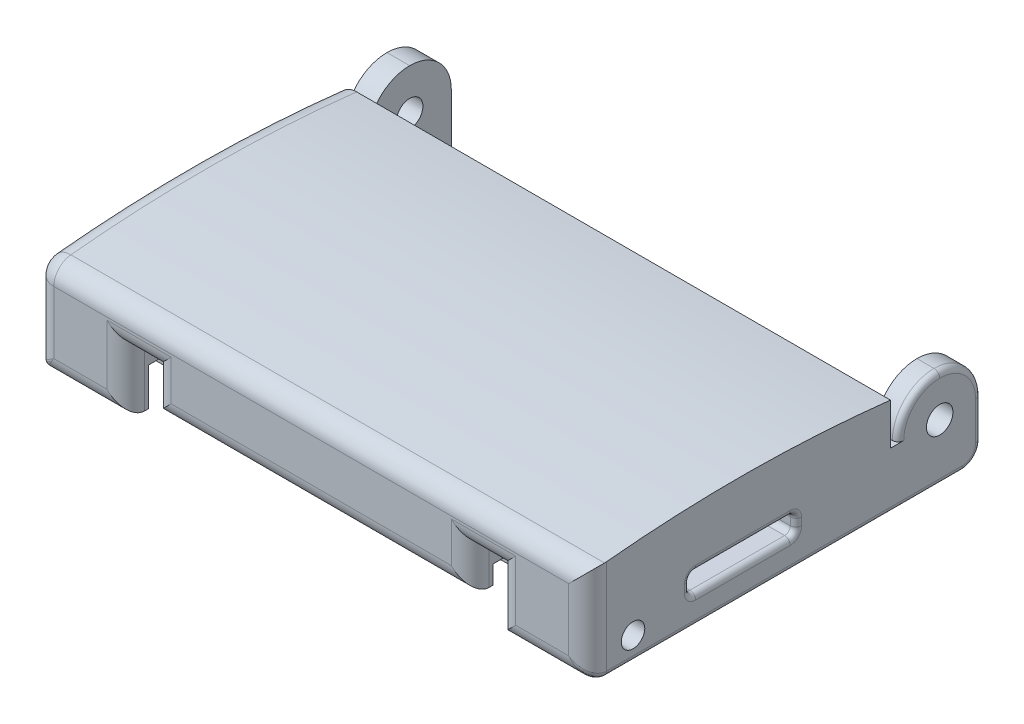
SolidWorks part; units mm, degrees
ref_plane "Front Plane" through (0, 0, 0) normal (0, 0, 1) x (1, 0, 0)
ref_plane "Top Plane" through (0, 0, 0) normal (0, 1, 0) x (1, 0, 0)
ref_plane "Right Plane" through (0, 0, 0) normal (1, 0, 0) x (0, 0, -1)
sketch "Sketch1" plane through (0, 0, 0) normal (0, 1, 0) x (1, 0, 0)
  line L1 (0, 0) -> (18.542, 0)
  line L2 (0, 0) -> (0, 10.16)
  line L3 (0, 10.16) -> (18.542, 10.16)
  line L4 (18.542, 0) -> (18.542, 10.16)
  dimension "D1" = 18.542
  dimension "D2" = 10.16
extrude "Extrude1" add sketch "Sketch1" along normal blind 3.302
sketch "Sketch2" plane through (18.542, 0, 0) normal (1, 0, 0) x (0, 0, -1)
  line L0 (10.16, 3.302) -> (10.16, 0) construction
  line L1 (0, 3.302) -> (10.16, 3.302) construction
  line L2 (0, 3.302) -> (0, 2.5771)
  line L3 (0, 3.302) -> (0, 0) construction
  line L4 (0, 2.5771) -> (10.16, 2.5771)
  line L5 (10.16, 2.5771) -> (10.16, 3.302)
  arc A0 (0, 3.302) -> (10.16, 3.302) centre (5.08, -41.3095) cw
  dimension "D1" = 44.6115
extrude "Extrude2" add sketch "Sketch2" against normal up to surface (18.542 mm away) up to face at (0, 1.651, -5.08)
sketch "Sketch3" plane through (0, 0, 0) normal (0, 0, 1) x (1, 0, 0)
  line L2 (15.494, 2.0076) -> (15.494, 0)
  line L3 (0, 0) -> (18.542, 0) construction
  line L4 (3.937, 0.6534) -> (14.605, 0.6534)
  line L5 (15.494, 0) -> (3.048, 0)
  line L8 (14.605, 0.6534) -> (14.605, 2.0076)
  line L9 (14.605, 2.0076) -> (15.494, 2.0076)
  line L12 (3.937, 0.6534) -> (3.937, 2.0076)
  line L13 (3.937, 2.0076) -> (3.048, 2.0076)
  line L14 (3.048, 0) -> (3.048, 2.0076)
  point P0 (9.271, 0)
  point P12 (9.271, 0.6534)
  dimension "D1" = 10.668
  dimension "D2" = 0.889
  dimension "D3" = 0.889
extrude "Extrude3" cut sketch "Sketch3" against normal blind 2.286
sketch "Sketch4" plane through (0, 0, 0) normal (0, -1, 0) x (1, 0, 0)
  line L0 (0, 0) -> (3.048, 0) construction
  line L1 (0.762, -2.286) -> (3.048, -2.286)
  line L2 (0.762, -2.286) -> (0.762, -0.762)
  line L3 (0.762, -0.762) -> (17.78, -0.762)
  line L4 (17.78, -2.286) -> (17.78, -0.762)
  line L5 (0, -10.16) -> (0, 0) construction
  line L6 (18.542, 0) -> (18.542, -10.16) construction
  line L7 (14.605, -2.286) -> (3.937, -2.286) construction
  line L8 (14.605, -2.286) -> (14.605, 0) construction
  line L9 (15.494, -2.286) -> (17.78, -2.286)
  line L10 (3.048, -2.286) -> (3.048, -3.129)
  line L11 (3.048, -3.129) -> (3.937, -3.129)
  line L12 (3.937, -2.286) -> (3.937, -3.129)
  line L14 (15.494, -2.286) -> (15.494, -3.129)
  line L15 (15.494, -3.129) -> (14.605, -3.129)
  line L16 (14.605, -2.286) -> (14.605, -3.129)
  line L17 (3.937, -2.286) -> (3.937, 0) construction
  line L18 (3.937, -2.286) -> (14.605, -2.286)
  dimension "D1" = 0.762
  dimension "D2" = 0.762
  dimension "D3" = 0.762
extrude "Extrude4" cut sketch "Sketch4" against normal blind 1.27
sketch "Sketch5" plane through (0.762, 0, 0) normal (1, 0, 0) x (0, 0, -1)
  line L0 (2.286, 0.7907) -> (0.762, 0.7907) construction
  line L1 (2.286, 1.27) -> (2.286, 0) construction
  line L2 (0.762, 1.27) -> (0.762, 0) construction
  circle A0 centre (1.524, 0.7907) radius 0.3937
  dimension "D1" = 0.7874
extrude "Extrude5" cut sketch "Sketch5" against normal mid plane 40.386
chamfer "Chamfer1" distance 0.762 angle 45 2 edges at (3.4925, 1.27, -2.286) (15.0495, 1.27, -2.286)
sketch "Sketch6" plane through (0, 0, 0) normal (0, -1, 0) x (1, 0, 0)
  line L0 (0, -5.08) -> (18.542, -5.08) construction
  line L1 (7.874, -3.1797) -> (10.668, -3.1797)
  line L2 (7.874, -3.1797) -> (7.874, -7.2437)
  line L3 (7.874, -7.2437) -> (10.668, -7.2437)
  line L4 (10.668, -3.1797) -> (10.668, -7.2437)
  line L5 (0, -10.16) -> (0, 0) construction
  line L6 (18.542, 0) -> (18.542, -10.16) construction
  point P10 (9.271, -5.08)
  point P11 (9.271, -3.1797)
  dimension "D1" = 2.794
  dimension "D2" = 4.064
extrude "Extrude6" cut sketch "Sketch6" against normal blind 2.54
sketch "Sketch7" plane through (10.668, 0, 0) normal (-1, 0, 0) x (0, 0, 1)
  line L0 (-6.9897, 1.5875) -> (-3.4337, 0.9525) construction
  line L1 (-3.4337, 0.9525) -> (-6.9897, 0.9525)
  line L2 (-3.4337, 0.9525) -> (-3.4337, 1.5875)
  line L3 (-3.4337, 1.5875) -> (-6.9897, 1.5875)
  line L4 (-6.9897, 0.9525) -> (-6.9897, 1.5875)
  line L5 (-7.2437, 0) -> (-3.1797, 2.54) construction
  point P8 (-5.2117, 1.27)
  point P9 (-5.2117, 1.27)
  dimension "D1" = 0.635
  dimension "D2" = 3.556
extrude "Extrude7" cut sketch "Sketch7" against normal mid plane 22.86
sketch "Sketch8" plane through (0, 0, 0) normal (0, -1, 0) x (1, 0, 0)
  line L0 (10.668, -3.1797) -> (7.874, -3.1797) construction
  line L1 (7.874, -7.2437) -> (10.668, -7.2437) construction
  line L2 (7.874, -3.1797) -> (7.874, -4.099)
  line L3 (7.874, -4.099) -> (7.874, -7.2437)
  line L4 (10.668, -7.2437) -> (10.668, -3.1797)
  arc A0 (7.874, -3.1797) -> (10.668, -3.1797) centre (9.271, -6.8945) cw
  arc A1 (7.874, -7.2437) -> (10.668, -7.2437) centre (9.271, -3.529) ccw
  point P8 (9.271, -7.4977)
  point P11 (9.271, -2.9257)
  point P12 (9.271, -3.1797)
  point P15 (9.271, -7.2437)
  dimension "D1" = 0.254
  dimension "D2" = 0.254
extrude "Extrude8" cut sketch "Sketch8" against normal up to surface (2.54 mm away) up to face at (9.271, 2.54, -5.2117)
fillet "Fillet1" radius 0.1905 24 edges at (18.542, 1.27, -6.9897) (10.668, 1.27, -6.9897) (18.542, 1.5875, -5.2117) (14.605, 1.5875, -6.9897) (10.668, 1.5875, -5.2117) (18.542, 0.9525, -5.2117) (10.668, 0.9525, -5.2117) (14.605, 0.9525, -6.9897) (18.542, 1.27, -3.4337) (14.605, 1.5875, -3.4337) (10.668, 1.27, -3.4337) (14.605, 0.9525, -3.4337) (0, 1.27, -6.9897) (7.874, 1.27, -6.9897) (0, 0.9525, -5.2117) (3.937, 0.9525, -6.9897) (7.874, 0.9525, -5.2117) (0, 1.27, -3.4337) (3.937, 0.9525, -3.4337) (7.874, 1.27, -3.4337) (0, 1.5875, -5.2117) (3.937, 1.5875, -3.4337) (7.874, 1.5875, -5.2117) (3.937, 1.5875, -6.9897)
sketch "Sketch9" plane through (0, 0, -10.16) normal (0, 0, -1) x (-1, 0, 0)
  line L1 (-18.542, 0) -> (-17.8308, 0)
  line L2 (-18.542, 0) -> (-18.542, 1.905)
  line L3 (-18.542, 1.905) -> (-17.8308, 1.905)
  line L4 (-17.8308, 0) -> (-17.8308, 1.905)
  dimension "D1" = 0.7112
  dimension "D2" = 1.905
extrude "Extrude9" add sketch "Sketch9" along normal blind 0.254
sketch "Sketch10" plane through (0, 0, -10.414) normal (0, 0, -1) x (-1, 0, 0)
  line L1 (-18.542, 0) -> (-17.78, 0)
  line L2 (-18.542, 0) -> (-18.542, 3.302)
  line L3 (-18.542, 3.302) -> (-17.78, 3.302)
  line L4 (-17.78, 0) -> (-17.78, 3.302)
  dimension "D1" = 3.302
extrude "Extrude10" add sketch "Sketch10" along normal blind 2.794
fillet "Fillet2" radius 1.397 2 edges at (18.161, 3.302, -10.414) (18.161, 3.302, -13.208)
sketch "Sketch11" plane through (18.542, 0, 0) normal (1, 0, 0) x (0, 0, -1)
  circle A0 centre (11.811, 1.905) radius 0.4445
  dimension "D1" = 0.889
extrude "Extrude11" cut sketch "Sketch11" against normal through all
ref_plane "Plane1" through (9.271, 0, 0) normal (-1, 0, 0) x (0, 0, 1)
mirror "Mirror1" about plane through (9.271, 0, 0) normal (-1, 0, 0) of "Extrude10", "Fillet2", "Extrude11", "Extrude9"
fillet "Fillet3" radius 0.635 15 edges at (0, 3.5903, -5.08) (0, 1.651, 0) (9.271, 3.302, 0) (18.542, 1.651, 0) (17.018, 0, 0) (1.524, 0, 0) (18.161, 0, -13.208) (14.605, 1.3305, 0) (9.271, 0.6534, 0) (3.937, 1.3305, 0) (3.4925, 2.0076, 0) (3.048, 1.0038, 0) (15.494, 1.0038, 0) (15.0495, 2.0076, 0)
fillet "Fillet4" radius 0.1905 8 edges at (0.186, 0.186, -0.186) (18.542, 2.8928, -12.7988) (18.542, 1.27, -13.208) (18.542, 0.186, -13.022) (0, 0, -6.9215) (18.542, 0, -6.604) (18.356, 0.186, -0.186)
